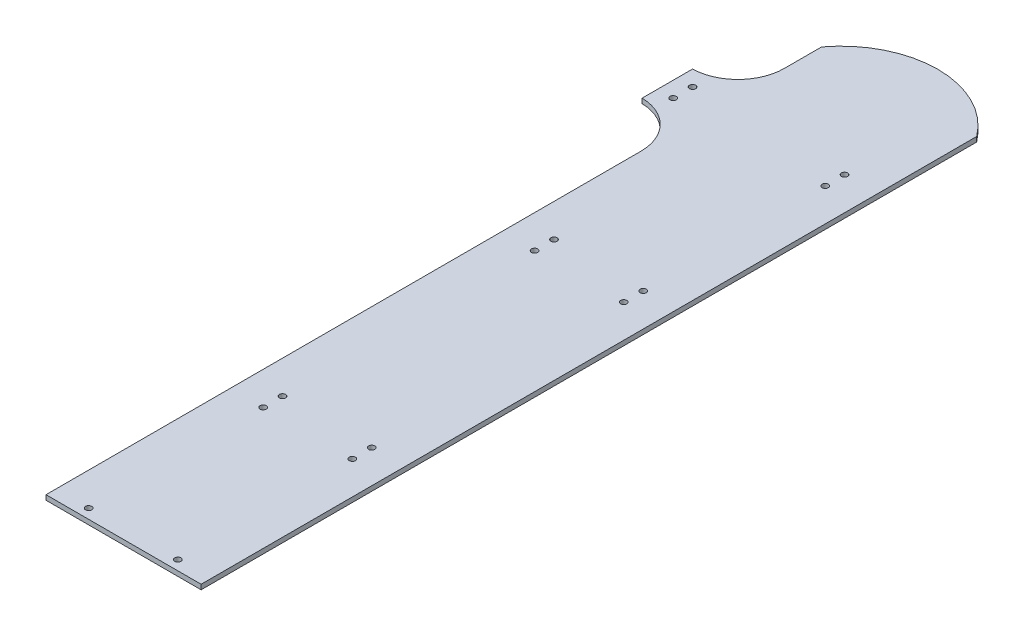
SolidWorks part; units mm, degrees
ref_plane "Front Plane" through (0, 0, 0) normal (0, 0, 1) x (1, 0, 0)
ref_plane "Top Plane" through (0, 0, 0) normal (0, 1, 0) x (1, 0, 0)
ref_plane "Right Plane" through (0, 0, 0) normal (1, 0, 0) x (0, 0, -1)
sketch "Sketch1" plane through (0, 0, 0) normal (0, 1, 0) x (1, 0, 0)
  line L2 (0, 0) -> (0, -508)
  line L3 (0, -508) -> (101.6, -508)
  line L4 (101.6, 0) -> (101.6, -508)
  arc A0 (0, 0) -> (101.6, 0) centre (50.8, -38.1) cw
  dimension "D3" = 63.5
  dimension "D1" = 508
  dimension "D2" = 101.6
extrude "Boss-Extrude1" add sketch "Sketch1" along normal blind 3.175
sketch "Sketch2" plane through (0, 0, 0) normal (0, -1, 0) x (1, 0, 0)
  line L0 (21.59, 82.55) -> (80.01, 82.55) construction
  line L1 (0, 508) -> (101.6, 508) construction
  circle A0 centre (21.59, 501.65) radius 2.032
  circle A1 centre (80.01, 501.65) radius 2.032
  circle A2 centre (21.59, 82.55) radius 2.032
  circle A3 centre (80.01, 82.55) radius 2.032
  arc A4 (0, 0) -> (101.6, 0) centre (50.8, 38.1) ccw construction
  circle A5 centre (21.59, 209.55) radius 2.032
  circle A6 centre (80.01, 209.55) radius 2.032
  circle A7 centre (21.59, 196.85) radius 2.032
  circle A8 centre (80.01, 196.85) radius 2.032
  circle A9 centre (21.59, 374.65) radius 2.032
  circle A10 centre (80.01, 374.65) radius 2.032
  circle A11 centre (21.59, 387.35) radius 2.032
  circle A12 centre (80.01, 387.35) radius 2.032
  point P11 (50.8, -25.4)
  point P12 (50.8, 82.55)
  dimension "D1" = 4.064
  dimension "D2" = 58.42
  dimension "D3" = 6.35
  dimension "D4" = 419.1
  dimension "D5" = 114.3
  dimension "D6" = 177.8
  dimension "D7" = 12.7
  dimension "D8" = 12.7
extrude "Cut-Extrude1" cut sketch "Sketch2" against normal through all
sketch "Sketch6" plane through (0, 3.175, 0) normal (0, 1, 0) x (1, 0, 0)
sketch "Sketch10" plane through (0, 0, 0) normal (0, -1, 0) x (-1, 0, 0)
  line L2 (0, 0) -> (76.2, 0)
  line L3 (0, 0) -> (0, -152.4)
  line L4 (0, -152.4) -> (76.2, -152.4)
  line L5 (76.2, 0) -> (76.2, -152.4)
  dimension "D1" = 152.4
  dimension "D2" = 76.2
extrude "Boss-Extrude6" add sketch "Sketch10" against normal up to surface (3.175 mm away) up to face at (80.01, 3.175, 207.518)
sketch "Sketch8" plane through (0, 0, 0) normal (0, -1, 0) x (-1, 0, 0)
  line L0 (-80.01, -80.518) -> (-80.01, -50.8583) construction
  line L1 (0, -508) -> (-101.6, -508) construction
  circle A0 centre (19.558, -77.6513) radius 2.032
  circle A1 centre (-80.01, -77.6513) radius 2.032
  circle A2 centre (19.558, -64.9513) radius 2.032
  circle A3 centre (-80.01, -64.9513) radius 2.032
  circle A4 centre (-80.01, -82.55) radius 2.032 construction
  dimension "D1" = 4.064
  dimension "D2" = 99.568
  dimension "D3" = 12.7
  dimension "D4" = 430.3487
extrude "Cut-Extrude4" cut sketch "Sketch8" against normal through all
sketch "Sketch16" plane through (0, 0, 0) normal (0, -1, 0) x (-1, 0, 0)
  line L0 (76.2, -152.4) -> (76.2, 0) construction
  line L1 (0, -152.4) -> (76.2, -152.4)
  line L2 (0, -152.4) -> (0, -87.8113)
  line L3 (0, -87.8113) -> (76.2, -87.8113)
  line L4 (76.2, -152.4) -> (76.2, -87.8113)
  line L6 (0, 0) -> (76.2, 0)
  line L7 (0, 0) -> (0, -54.7913)
  line L8 (0, -54.7913) -> (76.2, -54.7913)
  line L9 (76.2, 0) -> (76.2, -54.7913)
  line L10 (76.2, -87.8113) -> (29.718, -87.8113)
  line L11 (76.2, -87.8113) -> (76.2, -54.7913)
  line L12 (76.2, -54.7913) -> (29.718, -54.7913)
  line L13 (29.718, -87.8113) -> (29.718, -54.7913)
  circle A0 centre (19.558, -77.6513) radius 2.032 construction
  circle A1 centre (19.558, -64.9513) radius 2.032 construction
  line M27 (0, -152.4) -> (76.2, -152.4)
  line M28 (76.2, -152.4) -> (76.2, 0)
  line M29 (76.2, 0) -> (0, 0)
  dimension "D1" = 10.16
  dimension "D2" = 10.16
  dimension "D3" = 10.16
extrude "Cut-Extrude5" cut sketch "Sketch16" against normal through all contours L3 L2 M27 M28 | L13 L3 L8 M28 | L7 L8 M28 M29 region at (-38.1, 0, 120.1057) region at (-52.959, 0, 71.3013) region at (-38.1, 0, 27.3957)
sketch "Sketch17" plane through (0, 0, 0) normal (0, -1, 0) x (1, 0, 0)
  line L0 (101.6, 508) -> (101.6, 0) construction
  line L1 (16.9061, 86.7937) -> (27.1204, 86.7937)
  line L2 (16.9061, 86.7937) -> (16.9061, 77.309)
  line L3 (16.9061, 77.309) -> (27.1204, 77.309)
  line L4 (27.1204, 86.7937) -> (27.1204, 77.309)
  line L5 (75.0662, 85.45) -> (85.3535, 85.45)
  line L6 (75.0662, 85.45) -> (75.0662, 79.9167)
  line L7 (75.0662, 79.9167) -> (85.3535, 79.9167)
  line L8 (85.3535, 85.45) -> (85.3535, 79.9167)
  line L9 (0, 54.7913) -> (-29.718, 54.7913) construction
  line L10 (0, 87.8113) -> (0, 508) construction
  dimension "D1" = 5.5333
  dimension "D2" = 10.2873
  dimension "D3" = 16.2465
  dimension "D4" = 25.1254
  dimension "D5" = 10.2143
  dimension "D6" = 9.4847
  dimension "D7" = 16.9061
  dimension "D8" = 22.5176
extrude "Boss-Extrude11" add sketch "Sketch17" against normal up to surface (3.175 mm away) up to face at (80.01, 3.175, 75.6193)
fillet "Fillet1" radius 30.48 2 edges at (0, 1.5875, 87.8113) (0, 1.5875, 54.7913)
